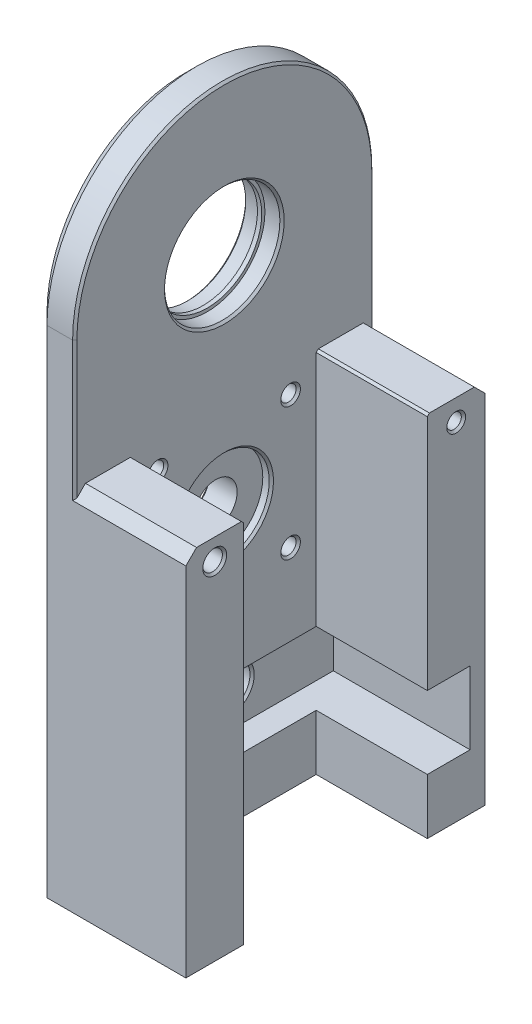
SolidWorks part; units mm, degrees
ref_plane "Ebene vorne" through (0, 0, 0) normal (0, 0, 1) x (1, 0, 0)
ref_plane "Ebene oben" through (0, 0, 0) normal (0, 1, 0) x (1, 0, 0)
ref_plane "Ebene rechts" through (0, 0, 0) normal (1, 0, 0) x (0, 0, -1)
sketch "Sketch2" plane through (0, 0, 0) normal (1, 0, 0) x (0, 0, -1)
  line L1 (0, 0) -> (70, 0)
  line L2 (0, 0) -> (0, 86)
  line L3 (0, 86) -> (70, 86)
  line L4 (70, 0) -> (70, 86)
  line L5 (0, 0) -> (70, 86) construction
  line L6 (0, 86) -> (70, 0) construction
  line L7 (0, 86) -> (70, 86)
  line L8 (0, 86) -> (0, 116)
  line L9 (0, 116) -> (70, 116)
  line L10 (70, 86) -> (70, 116)
  line L11 (0, 86) -> (70, 116) construction
  line L12 (0, 116) -> (70, 86) construction
  circle A0 centre (35, 116) radius 35
  circle A1 centre (35, 116) radius 12.75
  point P4 (35, 43)
  point P9 (35, 101)
  dimension "D4" = 25.5
  dimension "D1" = 70
  dimension "D2" = 86
  dimension "D3" = 30
extrude "Boss-Extrude1" add sketch "Sketch2" along normal blind 35 contours A0 L3 L2 L1 L4 | L7 A0 region at (0, 42.1521, -35) region at (0, 83.9872, -35)
sketch "Sketch9" plane through (35, 0, 0) normal (1, 0, 0) x (0, 0, -1)
  line L0 (13.5, 86) -> (13.5, 0)
  line L1 (0, 86) -> (70, 86) construction
  line L2 (0, 0) -> (70, 0) construction
  line L3 (13.5, 0) -> (56.5, 0)
  line L4 (56.5, 0) -> (56.5, 86)
  line L5 (56.5, 86) -> (13.5, 86)
  line L8 (35, 0) -> (35, 86) construction
  line L9 (13.5, 0) -> (56.5, 0)
  line L10 (13.5, 0) -> (13.5, 43)
  line L11 (13.5, 43) -> (56.5, 43)
  line L12 (56.5, 0) -> (56.5, 43)
  line L13 (13.5, 0) -> (56.5, 43) construction
  line L14 (13.5, 43) -> (56.5, 0) construction
  line L15 (56.5, 43) -> (13.5, 43)
  line L16 (56.5, 43) -> (56.5, 86)
  line L17 (56.5, 86) -> (13.5, 86)
  line L18 (13.5, 43) -> (13.5, 86)
  line L19 (56.5, 43) -> (13.5, 86) construction
  line L20 (56.5, 86) -> (13.5, 43) construction
  line L21 (56.5, 30) -> (66.5, 30)
  line L22 (56.5, 30) -> (56.5, 13)
  line L23 (56.5, 13) -> (66.5, 13)
  line L24 (66.5, 30) -> (66.5, 13)
  line L25 (56.5, 30) -> (66.5, 13) construction
  line L26 (56.5, 13) -> (66.5, 30) construction
  circle A0 centre (35, 64.5) radius 11
  circle A1 centre (35, 64.5) radius 5
  point P15 (35, 21.5)
  point P19 (35, 64.5)
  point P26 (61.5, 21.5)
  line M2 (70, 86) -> (0, 86)
  line M4 (0, 0) -> (70, 0)
  dimension "D3" = 22
  dimension "D4" = 10
  dimension "D5" = 17
  dimension "D6" = 10
extrude "Cut-Extrude1" cut sketch "Sketch9" against normal offset from surface (26 mm away) 9 contours L0 L11 L4 A0 M2 | A0 A1 | A1 | L11 L0 L4 M4 | L24 L21 L12 L23 region at (35, 85.3919, -35) region at (35, 21.5, -35) region at (35, 21.5, -61.5) region at (35, 64.5, -24.3111) region at (35, 64.5, -35) up to face at (0, 43, -35)
extrude "Boss-Extrude2" add sketch "Sketch2<5>" along normal up to surface (9 mm away) contours L9 A0 L7 | A0 L8 L3 | A0 L3 L10 | L9 A0 region at (0, 93.0889, -4.7772) region at (0, 93.0889, -65.2228) region at (0, 100.9401, -35) region at (0, 132.2994, -35) up to face at (9, 32.25, -48.25)
sketch "Sketch2<5>" plane through (0, 0, 0) normal (1, 0, 0) x (0, 0, -1) same geometry as "Sketch2"
extrude "Cut-Extrude2" cut sketch "Sketch9<3>" against normal offset from surface (28 mm away) 2 contours A0 A1 | A1 region at (35, 64.5, -24.3111) region at (35, 64.5, -35) up to face at (9, 58.0833, -43.8333) offset beyond the face yes
sketch "Sketch9<3>" plane through (35, 0, 0) normal (1, 0, 0) x (0, 0, -1) same geometry as "Sketch9"
extrude "Cut-Extrude3" cut sketch "Sketch9<4>" against normal through all contours A1 region at (35, 64.5, -35)
sketch "Sketch9<4>" plane through (35, 0, 0) normal (1, 0, 0) x (0, 0, -1) same geometry as "Sketch9"
sketch "Sketch20" plane through (9, 0, 0) normal (1, 0, 0) x (0, 0, -1)
  circle A0 centre (35, 116) radius 13.5
  dimension "D1" = 27
extrude "Cut-Extrude4" cut sketch "Sketch20" against normal blind 4
ref_plane "Plane1" through (4.5, 0, 0) normal (1, 0, 0) x (0, 0, -1)
mirror "Mirror1" about plane through (4.5, 0, 0) normal (1, 0, 0) of "Cut-Extrude4"
hole_wizard "CBORE for M3 Hex Socket Head Cap Screw1" positions "Sketch10" profile "Sketch11" counterbore size "M3" standard "DIN" end condition through all
sketch "Sketch10" plane through (0, 0, 0) normal (-1, 0, 0) x (0, 0, 1)
  line L1 (-50.5, 49) -> (-19.5, 49)
  line L2 (-50.5, 49) -> (-50.5, 80)
  line L3 (-50.5, 80) -> (-19.5, 80)
  line L4 (-19.5, 49) -> (-19.5, 80)
  line L5 (-50.5, 49) -> (-19.5, 80) construction
  line L6 (-50.5, 80) -> (-19.5, 49) construction
  point P1 (-35, 64.5)
  point P2 (-19.5, 80)
  point P5 (-50.5, 49)
  point P6 (-50.5, 80)
  point P7 (-19.5, 49)
  dimension "D1" = 31
sketch "Sketch11" plane through (0, 49, -19.5) normal (0, 1, 0) x (0, 0, 1)
  line L0 (0, 0) -> (0, 35)
  line L1 (0, 35) -> (1.8, 35)
  line L3 (1.8, 35) -> (1.8, 3.4)
  line L4 (1.8, 3.4) -> (3.25, 3.4)
  line L5 (3.25, 3.4) -> (3.25, 0)
  line L7 (3.25, 0) -> (0, 0)
  line L11 (0, -6.35) -> (0, 107.95) construction
  dimension "Thru Hole Dia." = 3.6
  dimension "Thru Hole Depth" = 35
  dimension "C'Bore Dia." = 6.5
  dimension "C'Bore Depth" = 3.4
hole_wizard "Ø4.6 (4.6) Diameter Hole1" positions "Sketch12" profile "Sketch13" hole size "Ø4.6" standard "DIN"
sketch "Sketch12" plane through (0, 0, 0) normal (0, -1, 0) x (-1, 0, 0)
  line L0 (-35, 70) -> (-35, 0) construction
  line L1 (-35, 0) -> (-35, 13.5) construction
  line L4 (-65.5, 6.5) -> (-4.5, 6.5)
  line L5 (-65.5, 6.5) -> (-65.5, 63.5)
  line L6 (-65.5, 63.5) -> (-4.5, 63.5)
  line L7 (-4.5, 6.5) -> (-4.5, 63.5)
  line L8 (-65.5, 6.5) -> (-4.5, 63.5) construction
  line L9 (-65.5, 63.5) -> (-4.5, 6.5) construction
  line L10 (-35, 70) -> (0, 70) construction
  line L11 (0, 0) -> (0, 70) construction
  point P6 (-35, 35)
  point P7 (-4.5, 63.5)
  point P12 (-4.5, 6.5)
  point P70 (-4.5, 35)
  dimension "D1" = 6.5
  dimension "D2" = 4.5
sketch "Sketch13" plane through (4.5, 0, -35) normal (1, 0, 0) x (0, 0, -1)
  line L0 (0, 0) -> (0, 7.382)
  line L1 (0, 7.382) -> (2.3, 6)
  line L2 (2.3, 6) -> (2.3, 0)
  line L5 (2.3, 0) -> (0, 0)
  line L10 (0, 7.382) -> (-2.3, 6) construction
  line L11 (0, -6.35) -> (0, 107.95) construction
  dimension "Hole Dia." = 4.6
  dimension "Hole Depth" = 6
  dimension "Drill Angle" = 118
hole_wizard "CBORE for M3 Hex Socket Head Cap Screw2" positions "Sketch16" profile "Sketch18" counterbore size "M3" standard "DIN" end condition through all
sketch "Sketch16" plane through (0, 0, 0) normal (-1, 0, 0) x (0, 0, 1)
  line L0 (-56.5, 86) -> (-70, 86) construction
  line L1 (-56.5, 86) -> (-70, 86)
  line L2 (-63.25, 86) -> (-63.25, 81) construction
  point P4 (-63.25, 81)
  dimension "D1" = 5
sketch "Sketch18" plane through (0, 81, -63.25) normal (0, 1, 0) x (0, 0, 1)
  line L0 (0, 0) -> (0, 35)
  line L1 (0, 35) -> (1.7, 35)
  line L3 (1.7, 35) -> (1.7, 21.4)
  line L4 (1.7, 21.4) -> (3.25, 21.4)
  line L5 (3.25, 21.4) -> (3.25, 0)
  line L7 (3.25, 0) -> (0, 0)
  line L11 (0, -6.35) -> (0, 107.95) construction
  dimension "Thru Hole Dia." = 3.4
  dimension "Thru Hole Depth" = 35
  dimension "C'Bore Dia." = 6.5
  dimension "C'Bore Depth" = 21.4
hole_wizard "Ø4.6 (4.6) Diameter Hole2" positions "Sketch14" profile "Sketch15" hole size "Ø4.6" standard "DIN"
sketch "Sketch14" plane through (35, 0, 0) normal (1, 0, 0) x (0, 0, -1)
  line L0 (6.75, 86) -> (6.75, 81) construction
  line L1 (0, 86) -> (13.5, 86) construction
  point P2 (6.75, 81)
  dimension "D1" = 5
sketch "Sketch15" plane through (35, 81, -6.75) normal (0, 1, 0) x (0, 0, -1)
  line L0 (0, 0) -> (0, 7.382)
  line L1 (0, 7.382) -> (2.3, 6)
  line L2 (2.3, 6) -> (2.3, 0)
  line L5 (2.3, 0) -> (0, 0)
  line L10 (0, 7.382) -> (-2.3, 6) construction
  line L11 (0, -6.35) -> (0, 107.95) construction
  dimension "Hole Dia." = 4.6
  dimension "Hole Depth" = 6
  dimension "Drill Angle" = 118
hole_wizard "Ø4.6 (4.6) Diameter Hole3" positions "Sketch21" profile "Sketch22" hole size "Ø4.6" standard "DIN"
sketch "Sketch21" plane through (0, 0, 0) normal (-1, 0, 0) x (0, 0, 1)
  line L0 (-35, 116.4443) -> (-35, 64.5) construction
  point P5 (-10, 89.5)
  point P9 (-60, 89.5)
  dimension "D1" = 25
  dimension "D2" = 25
sketch "Sketch22" plane through (0, 89.5, -60) normal (0, 1, 0) x (0, 0, 1)
  line L0 (0, 0) -> (0, 6.382)
  line L1 (0, 6.382) -> (2.3, 5)
  line L2 (2.3, 5) -> (2.3, 0)
  line L5 (2.3, 0) -> (0, 0)
  line L10 (0, 6.382) -> (-2.3, 5) construction
  line L11 (0, -6.35) -> (0, 107.95) construction
  dimension "Hole Dia." = 4.6
  dimension "Hole Depth" = 5
  dimension "Drill Angle" = 118
sketch "Sketch23" plane through (9, 0, 0) normal (1, 0, 0) x (0, 0, -1)
  line L0 (66.5, 13) -> (56.5, 13) construction
  line L1 (66.5, 30) -> (66.5, 13) construction
  line L2 (66.5, 30) -> (56.5, 30) construction
  line L3 (66.5, 13) -> (56.5, 13)
  line L4 (66.5, 30) -> (66.5, 13)
  line L5 (66.5, 30) -> (56.5, 30)
  line L6 (27.5, 21.5) -> (42.5, 21.5) construction
  line L7 (27.5, 26.5) -> (42.5, 26.5)
  line L8 (27.5, 16.5) -> (42.5, 16.5)
  line L10 (66.5, 13) -> (22.5, 13)
  line L11 (66.5, 13) -> (66.5, 30)
  line L12 (66.5, 30) -> (22.5, 30)
  line L13 (22.5, 13) -> (22.5, 30)
  line L14 (66.5, 13) -> (22.5, 30) construction
  line L15 (66.5, 30) -> (22.5, 13) construction
  arc A0 (27.5, 26.5) -> (27.5, 16.5) centre (27.5, 21.5) ccw
  arc A1 (42.5, 16.5) -> (42.5, 26.5) centre (42.5, 21.5) ccw
  point P6 (35, 21.5)
  point P14 (66.5, 21.5)
  point P16 (44.5, 21.5)
  point P18 (35, 64.5)
  line M19 (56.5, 13) -> (66.5, 13)
  line M20 (66.5, 13) -> (66.5, 30)
  line M21 (66.5, 30) -> (56.5, 30)
  dimension "D1" = 15
  dimension "D2" = 10
extrude "Cut-Extrude5" cut sketch "Sketch23" against normal blind 6 contours A1 L8 A0 L13 L10 L12 L7 M19 M20 M21 | L8 A1 L7 A0 region at (9, 21.5, -35) region at (9, 21.5, -48.6796)
extrude "Cut-Extrude6" cut sketch "Sketch23<3>" against normal up to next contours L8 A1 L7 A0 region at (9, 21.5, -35)
sketch "Sketch23<3>" plane through (9, 0, 0) normal (1, 0, 0) x (0, 0, -1) same geometry as "Sketch23"
chamfer "2,5mm Chamfer1" distance 2.5 angle 45 5 edges at (22, 86, -70) (22, 86, 0) (0, 58, -70) (0, 151, -35) (0, 58, 0)
chamfer "0,5mm Chamfer2" distance 0.5 angle 45 35 edges at (3.4, 49, -48.7) (9, 49, -52.3) (4.5, 0, -8.8) (4.5, 0, -37.3) (4.5, 0, -65.8) (9, 49, -21.3) (9, 64.5, -46) (35, 81, -9.05) (9, 80, -52.3) (35, 81, -61.55) (9, 80, -21.3) (0, 49, -16.25) (0, 49, -47.25) (0, 64.5, -40) (0, 81, -60) (0, 80, -47.25) (0, 80, -16.25) (22, 86, -13.5) (9, 99.75, -70) (9, 99.75, 0) (9, 151, -35) (0, 116, -48.5) (9, 116, -48.5) (22, 86, -56.5) (0, 89.5, -7.7) (0, 89.5, -57.7) (3, 26.5, -35) (3, 25.0355, -23.9645) (3, 21.5, -47.5) (3, 17.9645, -23.9645) (3, 16.5, -35) (0, 26.5, -35) (0, 21.5, -47.5) (0, 21.5, -22.5) (0, 16.5, -35)
